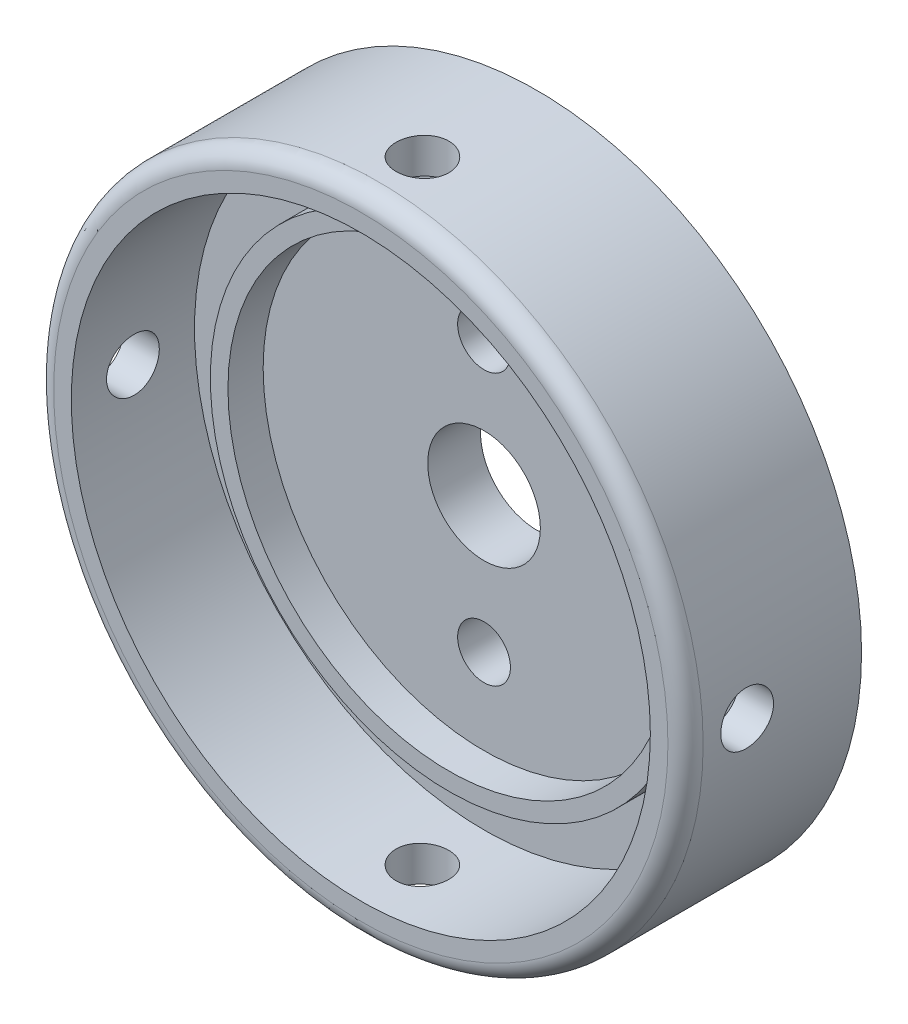
SolidWorks part; units mm, degrees
ref_plane "Plan de face" through (0, 0, 0) normal (0, 0, 1) x (1, 0, 0)
ref_plane "Plan de dessus" through (0, 0, 0) normal (0, 1, 0) x (1, 0, 0)
ref_plane "Plan de droite" through (0, 0, 0) normal (1, 0, 0) x (0, 0, -1)
sketch "Esquisse1" plane through (0, 0, 0) normal (0, 0, 1) x (1, 0, 0)
  line L3 (0, -1000) -> (0, 49000) construction
  line L4 (-1000, 0) -> (49000, 0) construction
  line L8 (-5.2, 0) -> (5.2, 0) construction
  arc A0 (-3.2, 0) -> (3.2, 0) centre (0, 0) ccw
  circle A1 centre (0, 0) radius 13.55
  circle A2 centre (0, 0) radius 16.45
  circle A3 centre (0, 0) radius 18.45
  circle A4 centre (0, 0) radius 12.55
  circle A5 centre (0, -7.7) radius 1.5
  circle A6 centre (0, 7.7) radius 1.5
  circle A16 centre (0, 0) radius 3.2
  point P7 (-8.6312, 16.3066)
  point P12 (0, 3.2)
  point P16 (0, 6.2)
  point P17 (0, -6.2)
  point P18 (0, -3.2)
  dimension "D1" = 3.2
  dimension "D2" = 27.1
  dimension "D3" = 32.9
  dimension "D4" = 25.1
  dimension "D5" = 3
  dimension "D6" = 3
  dimension "D8" = 3
  dimension "D7" = 3
extrude "Boss.-Extru.2" add sketch "Esquisse1" along normal blind 3 contours A0 A16 | A3 | A6 | A5 region at (0, 0, 0)
extrude "Boss.-Extru.4" add sketch "Esquisse1<13>" along normal blind 10 contours A3 A2 region at (-17.9282, 0, 0)
sketch "Esquisse1<13>" plane through (0, 0, 0) normal (0, 0, 1) x (1, 0, 0) same geometry as "Esquisse1"
extrude "Boss.-Extru.5" add sketch "Esquisse1<14>" along normal blind 5 contours A1 A4 region at (-13.1667, 0, 0)
sketch "Esquisse1<14>" plane through (0, 0, 0) normal (0, 0, 1) x (1, 0, 0) same geometry as "Esquisse1"
sketch "Esquisse2" plane through (0, 0, 0) normal (1, 0, 0) x (0, 0, -1)
  line L0 (0, 0) -> (-10, 0) construction
  circle A0 centre (-6.5, 0) radius 1.5
  dimension "D3" = 3
  dimension "D1" = 10
  dimension "D2" = 3.5
extrude "Enlèv. mat.-Extru.1" cut sketch "Esquisse2" against normal through all both and the other way through all
sketch "Esquisse3" plane through (0, 0, 0) normal (0, 1, 0) x (1, 0, 0)
  line L0 (0, 0) -> (0, -10) construction
  circle A0 centre (0, -6.5) radius 1.5
  dimension "D2" = 3
  dimension "D1" = 10
  dimension "D3" = 3.5
extrude "Enlèv. mat.-Extru.2" cut sketch "Esquisse3" against normal through all both and the other way through all
fillet "Congé1" radius 1 1 edges at (18.45, 0, 10)
